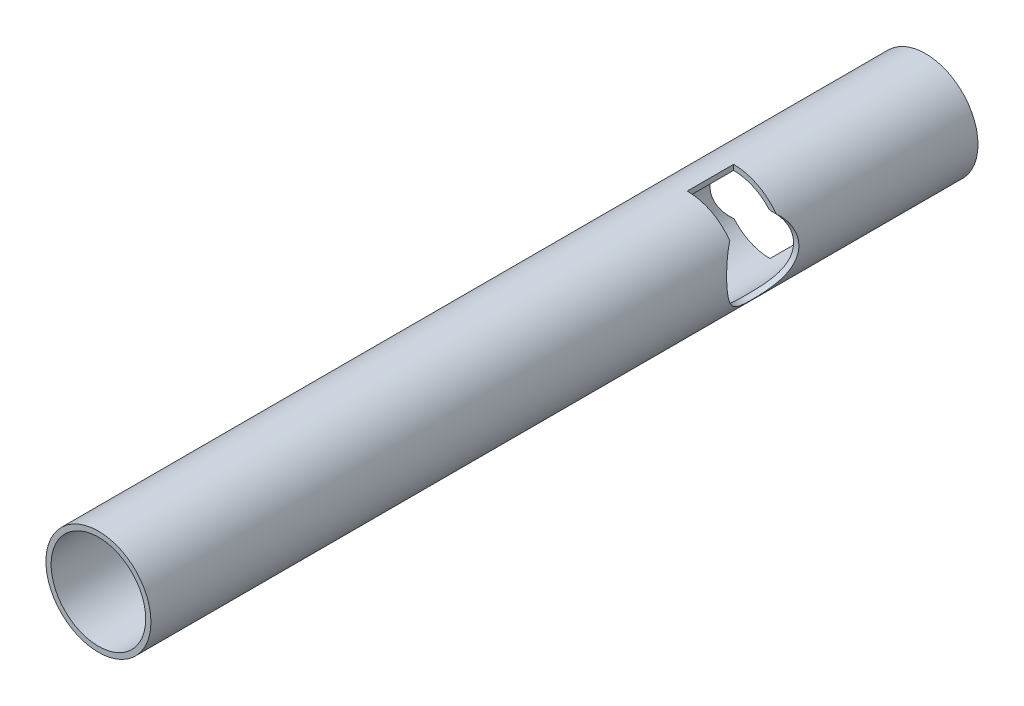
SolidWorks part; units mm, degrees
ref_plane "Front Plane" through (0, 0, 0) normal (0, 0, 1) x (1, 0, 0)
ref_plane "Top Plane" through (0, 0, 0) normal (0, 1, 0) x (1, 0, 0)
ref_plane "Right Plane" through (0, 0, 0) normal (1, 0, 0) x (0, 0, -1)
sketch "Sketch1" plane through (0, 0, 0) normal (0, 0, 1) x (1, 0, 0)
  circle A0 centre (0, 0) radius 31.75
  circle A1 centre (0, 0) radius 28.575
  dimension "D1" = 63.5
  dimension "D2" = 57.15
extrude "Boss-Extrude1" add sketch "Sketch1" along normal blind 250 and the other way blind 250 contours A1 | A0 region at (0, 0, 0)
sketch "Sketch2" plane through (0, 0, 0) normal (1, 0, 0) x (0, 0, -1)
  circle A2 centre (170, -2) radius 21.75
  dimension "D1" = 43.5
  dimension "D2" = 170
  dimension "D3" = 2
extrude "Cut-Extrude1" cut sketch "Sketch2" against normal through all
sketch "Sketch3" plane through (0, 0, 0) normal (1, 0, 0) x (0, 0, -1)
  circle A1 centre (120, 2) radius 21.75
  dimension "D1" = 120
  dimension "D2" = 43.5
  dimension "D3" = 2
extrude "Cut-Extrude2" cut sketch "Sketch3" along normal through all
sketch "Sketch5" plane through (0, 0, 0) normal (1, 0, 0) x (0, 0, -1)
  line L1 (184, -12.75) -> (156, -12.75)
  line L2 (184, -12.75) -> (184, -34.75)
  line L3 (184, -34.75) -> (156, -34.75)
  line L4 (156, -12.75) -> (156, -34.75)
  line L5 (184, -12.75) -> (156, -34.75) construction
  line L6 (184, -34.75) -> (156, -12.75) construction
  circle A0 centre (170, -2) radius 21.75 construction
  circle A1 centre (170, -2) radius 21.75 construction
  point P0 (170, -23.75)
  dimension "D1" = 28
  dimension "D2" = 22
  dimension "D3" = 170
extrude "Cut-Extrude4" cut sketch "Sketch5" against normal through all
sketch "Sketch6" plane through (0, 0, 0) normal (1, 0, 0) x (0, 0, -1)
  line L1 (106, 34.75) -> (134, 34.75)
  line L2 (106, 34.75) -> (106, 12.75)
  line L3 (106, 12.75) -> (134, 12.75)
  line L4 (134, 34.75) -> (134, 12.75)
  line L5 (106, 34.75) -> (134, 12.75) construction
  line L6 (106, 12.75) -> (134, 34.75) construction
  circle A0 centre (120, 2) radius 21.75 construction
  circle A1 centre (120, 2) radius 21.75 construction
  point P0 (120, 23.75)
  dimension "D1" = 28
  dimension "D2" = 22
  dimension "D3" = 120
extrude "Cut-Extrude5" cut sketch "Sketch6" along normal through all
